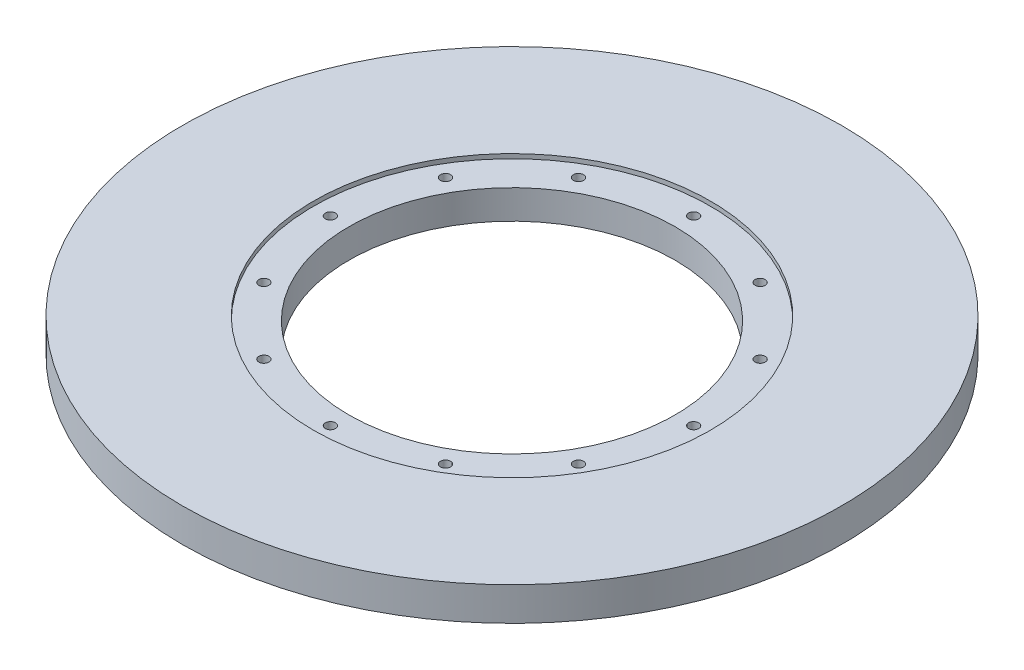
SolidWorks part; units mm, degrees
material "6061-T6 (SS)"
ref_plane "Front Plane" through (0, 0, 0) normal (0, 0, 1) x (1, 0, 0)
ref_plane "Top Plane" through (0, 0, 0) normal (0, 1, 0) x (1, 0, 0)
ref_plane "Right Plane" through (0, 0, 0) normal (1, 0, 0) x (0, 0, -1)
sketch "Sketch1" plane through (0, 0, 0) normal (0, 1, 0) x (1, 0, 0)
  line L5 (0, 0) -> (127.635, 0)
  line L6 (0, 0) -> (0, 127.635)
  line L7 (0, 127.635) -> (127.635, 127.635)
  line L8 (127.635, 0) -> (127.635, 127.635)
  dimension "D1" = 127.635
  dimension "D2" = 127.635
extrude "Boss-Extrude1" add sketch "Sketch1" along normal blind 9.525 contours L5 L8 L7 L6
sketch "Sketch13" plane through (0, 9.525, 0) normal (0, 1, 0) x (1, 0, 0)
  circle A0 centre (63.8175, 63.8175) radius 93.6625
  dimension "D1" = 187.325
extrude "Boss-Extrude2" add sketch "Sketch13" against normal up to surface (9.525 mm away) contours A0 up to face at (63.8175, 0, -63.8175)
sketch "Sketch6" plane through (127.635, 0, 0) normal (1, 0, 0) x (0, 0, -1)
  circle A0 centre (4.7625, 4.7625) radius 1.3526
  dimension "D1" = 2.7051
extrude "6-32 hole1" cut sketch "Sketch6" against normal blind 12.7
sketch "Sketch7" [suppressed] plane through (0, 0, -127.635) normal (0, 0, -1) x (-1, 0, 0)
  circle A0 centre (-122.8725, 4.7625) radius 1.3525
  dimension "D1" = 2.7051
sketch "Sketch8" [suppressed] plane through (0, 0, 0) normal (-1, 0, 0) x (0, 0, 1)
  circle A0 centre (-122.8725, 4.7625) radius 1.3525
  dimension "D1" = 2.7051
sketch "Sketch9" [suppressed] plane through (0, 0, 0) normal (0, 0, 1) x (1, 0, 0)
  circle A0 centre (4.7625, 4.7625) radius 1.3526
  dimension "D1" = 2.7051
sketch "Sketch5" plane through (0, 9.525, 0) normal (0, 1, 0) x (1, 0, 0)
  circle A0 centre (63.8175, 63.8175) radius 46.355
  circle A1 centre (63.8175, 63.8175) radius 93.6625 construction
  dimension "D1" = 92.71
extrude "Cut-Extrude1" cut sketch "Sketch5" against normal blind 9.525
sketch "Sketch11" plane through (0, 9.525, 0) normal (0, 1, 0) x (1, 0, 0)
  line L0 (63.8175, 63.8175) -> (63.8175, 115.443) construction
  circle A0 centre (63.8175, 115.443) radius 1.4351
  dimension "D2" = 2.8702
  dimension "D1" = 51.6255
extrude "Cut-Extrude3" cut sketch "Sketch11" against normal through all contours A0
pattern_circular "CirPattern1" count 12 over 360 about axis through (63.8175, 9.525, -63.8175) along (0, 1, 0) of "Cut-Extrude3"
sketch "Sketch12" plane through (0, 9.525, 0) normal (0, 1, 0) x (1, 0, 0)
  circle A0 centre (63.8175, 63.8175) radius 56.4198
  dimension "D1" = 112.8395
extrude "Cut-Extrude4" cut sketch "Sketch12" against normal blind 1.27
